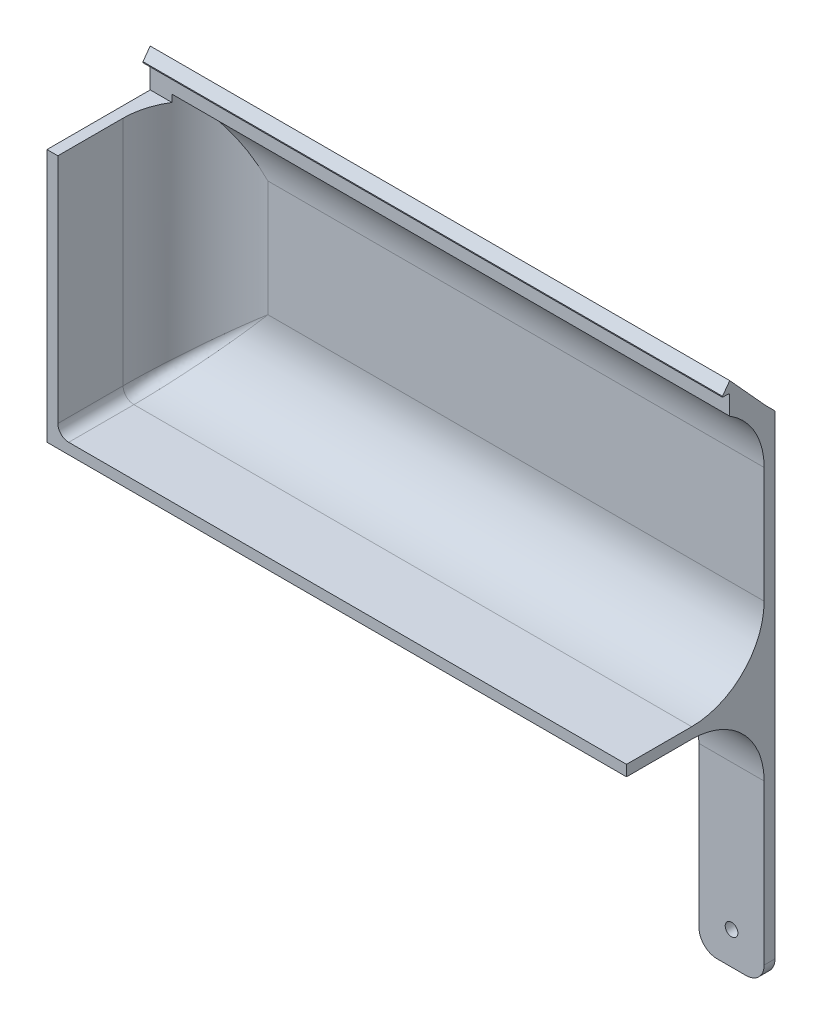
SolidWorks part; units mm, degrees
material "ABS"
ref_plane "Top Plane" through (0, 0, 0) normal (0, 0, 1) x (1, 0, 0)
ref_plane "Front Plane" through (0, 0, 0) normal (0, 1, 0) x (1, 0, 0)
ref_plane "Right Plane" through (0, 0, 0) normal (1, 0, 0) x (0, 0, -1)
sketch "Sketch1" plane through (0, 0, 0) normal (0, 0, 1) x (1, 0, 0)
  line L1 (-80, -37.5) -> (80, -37.5)
  line L2 (-80, -37.5) -> (-80, 37.5)
  line L3 (-80, 37.5) -> (80, 37.5)
  line L4 (80, -37.5) -> (80, 37.5)
  line L5 (-80, -37.5) -> (80, 37.5) construction
  line L6 (-80, 37.5) -> (80, -37.5) construction
  point P0 (0, 0)
  dimension "D1" = 75
  dimension "D2" = 160
extrude "baseplate" add sketch "Sketch1" along normal blind 3
sketch "Sketch2" plane through (0, 0, 3) normal (0, 0, 1) x (1, 0, 0)
  line L0 (-80, 37.5) -> (-80, -37.5)
  line L1 (-80, -37.5) -> (80, -37.5)
  line L2 (80, -37.5) -> (80, 37.5) construction
  line L3 (-80, -37.5) -> (80, -37.5) construction
  line L4 (80, -37.5) -> (80, -34.5)
  line L5 (80, -34.5) -> (-77, -34.5)
  line L6 (-77, -34.5) -> (-77, 37.5)
  line L7 (80, 37.5) -> (-80, 37.5) construction
  line L8 (-77, 37.5) -> (-80, 37.5)
  dimension "D1" = 3
  dimension "D2" = 3
extrude "draft wall" add sketch "Sketch2" along normal blind 38
fillet "inner corner fillet" radius 3 1 edges at (-77, -34.5, 22)
fillet "inner upstream fillet" radius 20 3 edges at (3, -34.5, 3) (-76.1213, -33.6213, 3) (-77, 3, 3)
sketch "Sketch5" plane through (0, 0, 3) normal (0, 0, 1) x (1, 0, 0)
  line L0 (-80, 37.5) -> (-80, -37.5) construction
  line L1 (80, 37.5) -> (-80, 37.5)
  line L2 (80, 37.5) -> (80, 34.5)
  line L3 (80, 34.5) -> (-80, 34.5)
  line L4 (-80, 37.5) -> (-80, 34.5)
  dimension "D1" = 3
extrude "holder notch base" add sketch "Sketch5" along normal blind 4.5
sketch "Sketch6" plane through (0, 0, 7.5) normal (0, 0, 1) x (1, 0, 0)
  line L1 (80, 34.5) -> (-80, 34.5)
  line L2 (80, 34.5) -> (80, 43)
  line L3 (80, 43) -> (-80, 43)
  line L4 (-80, 34.5) -> (-80, 43)
  dimension "D1" = 8.5
extrude "holder notch extension" add sketch "Sketch6" along normal blind 5
sketch "Sketch7" plane through (80, 0, 0) normal (1, 0, 0) x (0, 0, -1)
  line L0 (-12.5, 40) -> (-14.5, 40)
  line L1 (-12.5, 34.5) -> (-12.5, 43) construction
  line L3 (-14.5, 40.2634) -> (-14.5, 40)
  line L5 (-12.5, 40) -> (-12.5, 43)
  line L6 (-14.5, 40.2634) -> (-12.5, 43)
  dimension "D1" = 3
  dimension "D2" = 2
extrude "holder notch" add sketch "Sketch7" against normal up to surface (160 mm away) up to face at (-80, 20.125, 15.25)
sketch "Sketch8" plane through (-80, 0, 0) normal (-1, 0, 0) x (0, 0, 1)
  line L0 (12.5, 43) -> (7.5, 37.5)
  line L6 (7.5, 37.5) -> (7.5, 43)
  line L8 (7.5, 43) -> (12.5, 43)
extrude "holder notch assembly cutout" cut sketch "Sketch8" against normal through all
fillet "holder notch small stabilizer fillet" radius 0.5 1 edges at (0, 40, 12.5)
sketch "Sketch10" plane through (-80, 0, 0) normal (-1, 0, 0) x (0, 0, 1)
  line L1 (41, 37.5) -> (12.5, 37.5)
  line L2 (41, 37.5) -> (41, 32.5)
  line L3 (41, 32.5) -> (12.5, 32.5)
  line L4 (12.5, 37.5) -> (12.5, 32.5)
  dimension "D1" = 5
extrude "draft wall assembly cutout" cut sketch "Sketch10" against normal through all
sketch "Sketch12" plane through (0, 0, 0) normal (0, 0, -1) x (-1, 0, 0)
  line L1 (80, -37.5) -> (107, -37.5)
  line L2 (80, -37.5) -> (80, -19.5)
  line L3 (80, -19.5) -> (107, -19.5)
  line L4 (107, -37.5) -> (107, -19.5)
  line L5 (-80, -37.5) -> (-62, -37.5)
  line L6 (-80, -37.5) -> (-80, -106.5)
  line L7 (-80, -106.5) -> (-62, -106.5)
  line L8 (-62, -37.5) -> (-62, -106.5)
  dimension "D1" = 27
  dimension "D2" = 18
  dimension "D3" = 69
  dimension "D4" = 18
extrude "base holders" add sketch "Sketch12" against normal blind 3
fillet "base holder fillets" radius 5 4 edges at (80, -106.5, 1.5) (62, -106.5, 1.5) (-107, -19.5, 1.5) (-107, -37.5, 1.5)
fillet "base holder large fillets" radius 20 3 edges at (-80, -19.5, 1.5) (62, -37.5, 1.5) (71, -37.5, 3)
fillet "base holder large fillets 2" radius 10 1 edges at (-80, -18.5, 3)
sketch "Sketch13" plane through (0, 0, 3) normal (0, 0, 1) x (1, 0, 0)
  line L0 (-107, -32.5) -> (-107, -24.5) construction
  line L1 (75, -106.5) -> (67, -106.5) construction
  line L2 (62, -101.5) -> (62, -57.5) construction
  line L3 (-90, -37.5) -> (-102, -37.5) construction
  circle A0 centre (-98, -28.5) radius 1.75
  circle A1 centre (71, -97.5) radius 1.75
  dimension "D4" = 9
  dimension "D5" = 3.5
  dimension "D6" = 3.5
  dimension "D1" = 9
  dimension "D2" = 9
  dimension "D3" = 9
extrude "base holder screw mounts" cut sketch "Sketch13" against normal through all
fillet "Fillet7" radius 20 1 edges at (11.5, 34.5, 3)
chamfer "Chamfer1" distance 8 angle 45 1 edges at (0, 37.5, 0)
